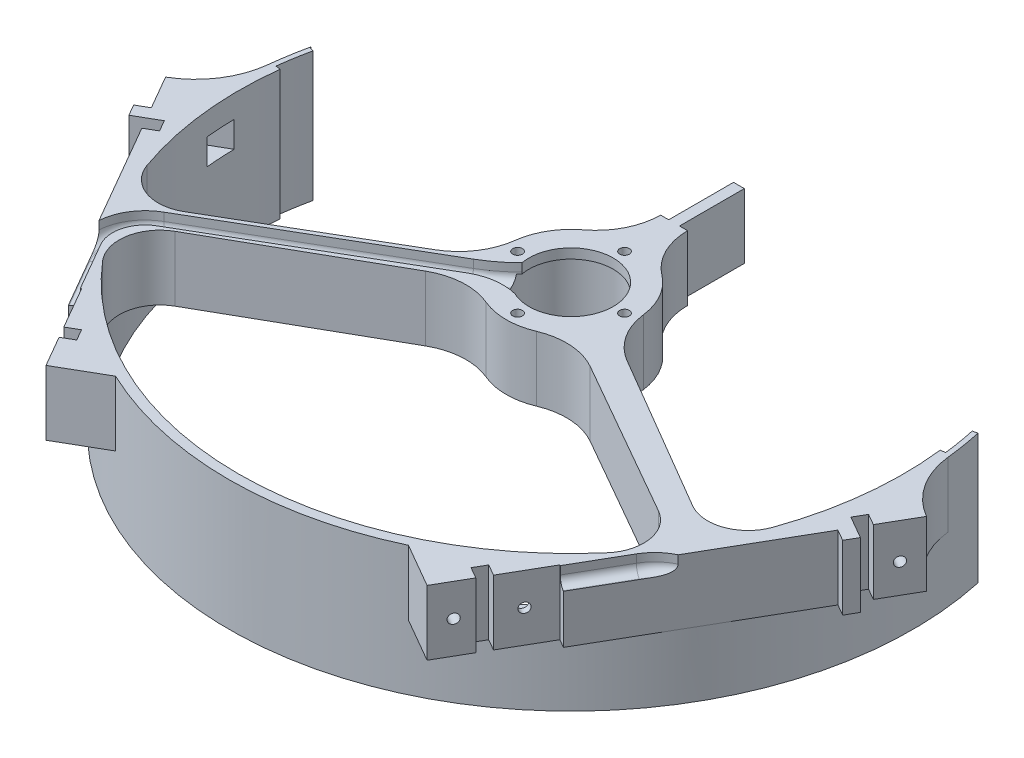
SolidWorks part; units mm, degrees
ref_plane "Plan de face" through (0, 0, 0) normal (0, 0, 1) x (1, 0, 0)
ref_plane "Plan de dessus" through (0, 0, 0) normal (0, 1, 0) x (1, 0, 0)
ref_plane "Plan de droite" through (0, 0, 0) normal (1, 0, 0) x (0, 0, -1)
sketch "Esquisse2" plane through (0, 0, 0) normal (0, 1, 0) x (1, 0, 0)
  circle A0 centre (0, 0) radius 105.5
  dimension "D1" = 211
extrude "Boss.-Extru.1" add sketch "Esquisse2" along normal blind 20
sketch "Esquisse3" plane through (0, 20, 0) normal (0, 1, 0) x (1, 0, 0)
  line L0 (0, 0) -> (0, -37.8201) construction
  line L1 (-22.2901, -5) -> (26.3096, -5) construction
  line L3 (-25.4411, -19.4651) -> (-74.7068, -47.4761)
  line L4 (25.4084, -19.5127) -> (74.6164, -47.6194)
  arc A0 (-78.0463, -66.4457) -> (77.919, -66.5949) centre (0, 0) ccw
  circle A1 centre (0, 0) radius 105.5 construction
  arc A2 (-74.7068, -47.4761) -> (-78.0463, -66.4457) centre (-68.5285, -58.3425) ccw
  arc A3 (77.919, -66.5949) -> (74.6164, -47.6194) centre (68.4167, -58.4736) ccw
  arc A5 (-7.7779, -18.4256) -> (7.7444, -18.4397) centre (0, 0) ccw
  arc A7 (-25.4411, -19.4651) -> (-7.7779, -18.4256) centre (-15.5558, -36.8513) cw
  arc A8 (7.7444, -18.4397) -> (25.4084, -19.5127) centre (15.4889, -36.8795) cw
  point P16 (0, -5)
  dimension "D3" = 102.5
  dimension "D6" = 25
  dimension "D2" = 25
  dimension "D5" = 20
  dimension "D7" = 20
  dimension "D1" = 5
extrude "Enlèv. mat.-Extru.1" cut sketch "Esquisse3" against normal through all
pattern_circular "Répétition circulaire1" count 3 over 360 about axis through (0, 20, 0) along (0, 1, 0) of "Enlèv. mat.-Extru.1"
sketch "Esquisse4" plane through (0, 20, 0) normal (0, 1, 0) x (1, 0, 0)
  circle A0 centre (-16.5, 0) radius 1.5
  circle A1 centre (16.5, 0) radius 1.5
  circle A2 centre (0, 16.5) radius 1.5
  circle A3 centre (0, -16.5) radius 1.5
  dimension "D1" = 3
  dimension "D2" = 3
  dimension "D5" = 3
  dimension "D6" = 3
  dimension "D3" = 16.5
  dimension "D4" = 16.5
  dimension "D7" = 16.5
  dimension "D8" = 16.5
extrude "Enlèv. mat.-Extru.2" cut sketch "Esquisse4" against normal through all
sketch "Esquisse5" plane through (0, 20, 0) normal (0, 1, 0) x (1, 0, 0)
  circle A0 centre (0, 0) radius 13
  dimension "D1" = 26
extrude "Enlèv. mat.-Extru.3" cut sketch "Esquisse5" against normal blind 3
sketch "Esquisse6" plane through (0, 17, 0) normal (0, 1, 0) x (1, 0, 0)
  circle A0 centre (0, 0) radius 14
extrude "Enlèv. mat.-Extru.4" cut sketch "Esquisse6" against normal through all
sketch "Esquisse7" plane through (0, 20, 0) normal (0, 1, 0) x (1, 0, 0)
  line L0 (-16.5, 0) -> (0, -16.5) construction
  line L1 (-73.3003, -42.3791) -> (-18.5313, -10.4184) construction
  line L2 (-78.5478, -40.81) -> (-29.6027, -12.2479) construction
  line L3 (-24.4395, -2.3515) -> (-11.5191, -24.4923) construction
  line L4 (-22.6547, -9.9301) -> (-17.499, -6.9215) construction
  line L5 (-14.9362, -11.215) -> (-21.6686, -15.1437) construction
  line L6 (-78.7767, -48.7003) -> (-18.5358, -13.5465)
  line L7 (-78.7767, -48.7003) -> (-81.4978, -44.0373)
  line L9 (-81.4978, -44.0373) -> (-21.257, -8.8835)
  line L10 (-78.7767, -48.7003) -> (-21.257, -8.8835) construction
  line L11 (-18.5358, -13.5465) -> (-81.4978, -44.0373) construction
  line L12 (-8.25, -8.25) -> (-5.2218, -5.2218) construction
  line L13 (-11.0784, -5.4216) -> (-9.3631, -3.7063) construction
  line L14 (-5.4216, -11.0784) -> (-2.758, -8.4149) construction
  line L15 (-12.4833, -2.3515) -> (-2.758, -12.7041)
  line L16 (-12.4833, -2.3515) -> (-12.7856, -2.3515)
  circle A0 centre (0, 0) radius 13 construction
  arc A1 (-21.257, -8.8835) -> (-12.7856, -2.3515) centre (-42.2756, 27.1348) ccw
  arc A2 (-18.5358, -13.5465) -> (-2.758, -12.7041) centre (-9.8276, -28.4693) cw
  point P14 (-47.6812, -27.4289)
  point P16 (-50.0168, -28.7919)
  dimension "D1" = 4
  dimension "D2" = 2.5
  dimension "D3" = 2.5
  dimension "D4" = 4
  dimension "D5" = 4
extrude "Enlèv. mat.-Extru.5" cut sketch "Esquisse7" against normal blind 5
sketch "Esquisse9" plane through (0, 0, 0) normal (0, -1, 0) x (1, 0, 0)
  line L0 (-117.3657, 7.7167) -> (-111.3657, 18.109)
  line L1 (0, 0) -> (-127.9608, 73.8782) construction
  line L2 (-131.1472, 15.6735) -> (-96.8675, -4.118) construction
  line L4 (-111.3657, 18.109) -> (-107.9016, 16.109)
  line L5 (-107.3657, 25.0372) -> (-103.9016, 23.0372)
  line L6 (-107.9016, 16.109) -> (-103.9016, 23.0372)
  line L7 (-107.3657, 25.0372) -> (-91.3657, 52.75)
  circle A0 centre (0, 0) radius 105.5 construction
  arc A1 (-104.8789, -11.4306) -> (-117.3657, 7.7167) centre (-130.0012, -14.1687) ccw
  arc A2 (-91.3657, 52.75) -> (-104.8789, -11.4306) centre (0, 0) ccw
  point P4 (-91.3657, 52.75)
  point P9 (-117.3657, 7.7167)
  dimension "D3" = 32
  dimension "D2" = 0
  dimension "D4" = 8
  dimension "D5" = 4
  dimension "D6" = 52.75
extrude "Boss.-Extru.4" add sketch "Esquisse9" against normal blind 20
sketch "Esquisse11" plane through (-91.3657, 0, 52.75) normal (-0.866, 0, 0.5) x (0.5, 0, 0.866)
  line L0 (-40, 0) -> (-52, 0) construction
  line L1 (-50, 5) -> (-42, 5)
  line L2 (-50, 5) -> (-50, 13)
  line L3 (-50, 13) -> (-42, 13)
  line L4 (-42, 5) -> (-42, 13)
  line L6 (-52, 20) -> (-52, 0) construction
  dimension "D1" = 8
  dimension "D2" = 8
  dimension "D3" = 5
  dimension "D4" = 2
extrude "Enlèv. mat.-Extru.6" cut sketch "Esquisse11" against normal blind 20
sketch "Esquisse12" plane through (-91.3657, 0, 52.75) normal (-0.866, 0, 0.5) x (0.5, 0, 0.866)
  line L0 (-40, 20) -> (-40, 0) construction
  line L1 (-50.7054, 3.9045) -> (-40, 3.9045)
  line L2 (-50.7054, 3.9045) -> (-50.7054, 16.1116)
  line L3 (-50.7054, 16.1116) -> (-40, 16.1116)
  line L4 (-40, 3.9045) -> (-40, 16.1116)
extrude "Boss.-Extru.5" add sketch "Esquisse12" against normal blind 5
sketch "Esquisse13" plane through (-87.0356, 0, 50.25) normal (0.866, 0, -0.5) x (-0.5, 0, -0.866)
  line L0 (50, 5) -> (42, 5) construction
  line L2 (42, 5) -> (42, 13) construction
  circle A0 centre (46, 9) radius 1.5
  point P7 (42, 10.6595)
  point P8 (44.4531, 9.3264)
  dimension "D1" = 3
  dimension "D2" = 4
  dimension "D3" = 4
extrude "Enlèv. mat.-Extru.7" cut sketch "Esquisse13" against normal through all
sketch "Esquisse22" plane through (0, 20, 0) normal (0, 1, 0) x (1, 0, 0)
  line L0 (-91.3657, -52.75) -> (-78.8757, -74.3833)
  line L1 (-78.8757, -74.3833) -> (-76.2776, -72.8833)
  line L2 (-76.2776, -72.8833) -> (-70.2776, -83.2756)
  line L3 (-58.7776, -103.1942) -> (-45.1731, -95.3396)
  line L4 (-75.8355, -73.3432) -> (-78.0603, -67.6298)
  line L5 (-78.0603, -67.6298) -> (-81.7873, -66.6415)
  line L9 (-68.7776, -85.8737) -> (-58.7776, -103.1942)
  line L10 (-70.2776, -83.2756) -> (-68.7776, -85.8737)
  arc A0 (-91.3657, -52.75) -> (-104.8789, 11.4306) centre (0, 0) ccw construction
  arc A1 (-91.3657, -52.75) -> (-81.7873, -66.6415) centre (0, 0) ccw
  arc A5 (-75.8355, -73.3432) -> (-45.1731, -95.3396) centre (0, 0) ccw
  point P6 (-76.2776, -72.8833)
  dimension "D1" = 3
  dimension "D2" = 35
extrude "Boss.-Extru.11" add sketch "Esquisse22" against normal blind 20
sketch "Esquisse25" plane through (-88.7676, 0, 51.25) normal (-0.866, 0, 0.5) x (0.5, 0, 0.866)
  line L0 (59.98, 0) -> (59.98, 20) construction
  line L1 (49.98, 6) -> (57.98, 6)
  line L2 (49.98, 6) -> (49.98, 14)
  line L3 (49.98, 14) -> (57.98, 14)
  line L4 (57.98, 6) -> (57.98, 14)
  line L5 (24.98, 20) -> (59.98, 20) construction
  dimension "D1" = 2
  dimension "D2" = 8
  dimension "D3" = 8
  dimension "D4" = 6
extrude "Enlèv. mat.-Extru.21" cut sketch "Esquisse25" against normal blind 20
sketch "Esquisse26" plane through (-88.7676, 0, 51.25) normal (-0.866, 0, 0.5) x (0.5, 0, 0.866)
  line L1 (49.98, 6) -> (57.98, 6)
  line L2 (49.98, 6) -> (49.98, 14)
  line L3 (49.98, 14) -> (57.98, 14)
  line L4 (57.98, 6) -> (57.98, 14)
extrude "Boss.-Extru.12" add sketch "Esquisse26" against normal blind 4
sketch "Esquisse28" plane through (-85.3035, 0, 49.25) normal (0.866, 0, -0.5) x (-0.5, 0, -0.866)
  line L0 (-49.98, 14) -> (-49.98, 6) construction
  line L1 (-49.98, 6) -> (-57.98, 6) construction
  circle A0 centre (-53.98, 10) radius 1.5
  dimension "D1" = 3
  dimension "D2" = 4
  dimension "D3" = 4
extrude "Enlèv. mat.-Extru.22" cut sketch "Esquisse28" against normal through all
sketch "Esquisse29" plane through (-88.7676, 0, 51.25) normal (-0.866, 0, 0.5) x (0.5, 0, 0.866)
  line L0 (24.98, 0) -> (59.98, 0) construction
  line L1 (44.98, 0) -> (48.98, 0)
  line L2 (44.98, 0) -> (44.98, 20)
  line L3 (44.98, 20) -> (48.98, 20)
  line L4 (48.98, 0) -> (48.98, 20)
  line L5 (24.98, 20) -> (59.98, 20) construction
  line L7 (59.98, 0) -> (59.98, 20) construction
  dimension "D1" = 4
  dimension "D2" = 11
extrude "Enlèv. mat.-Extru.23" cut sketch "Esquisse29" against normal blind 4
sketch "Esquisse30" plane through (-88.7676, 0, 51.25) normal (-0.866, 0, 0.5) x (0.5, 0, 0.866)
  line L0 (44.98, 20) -> (44.98, 0) construction
  line L1 (41.98, 6) -> (33.98, 6)
  line L2 (41.98, 6) -> (41.98, 14)
  line L3 (41.98, 14) -> (33.98, 14)
  line L4 (33.98, 6) -> (33.98, 14)
  line L5 (24.98, 20) -> (44.98, 20) construction
  dimension "D1" = 3
  dimension "D2" = 8
  dimension "D3" = 8
  dimension "D4" = 6
extrude "Enlèv. mat.-Extru.24" cut sketch "Esquisse30" against normal blind 23
sketch "Esquisse31" plane through (-88.7676, 0, 51.25) normal (-0.866, 0, 0.5) x (0.5, 0, 0.866)
  line L1 (33.98, 6) -> (41.98, 6)
  line L2 (33.98, 6) -> (33.98, 14)
  line L3 (33.98, 14) -> (41.98, 14)
  line L4 (41.98, 6) -> (41.98, 14)
extrude "Boss.-Extru.13" add sketch "Esquisse31" against normal blind 2
sketch "Esquisse32" plane through (-87.0356, 0, 50.25) normal (0.866, 0, -0.5) x (-0.5, 0, -0.866)
  line L0 (-33.98, 6) -> (-41.98, 6) construction
  line L1 (-33.98, 14) -> (-33.98, 6) construction
  circle A0 centre (-37.98, 10) radius 1.5
  dimension "D1" = 3
  dimension "D2" = 4
  dimension "D3" = 4
extrude "Enlèv. mat.-Extru.25" cut sketch "Esquisse32" against normal blind 22
sketch "Esquisse33" plane through (12.49, 0, 21.6333) normal (0.5, 0, 0.866) x (0.866, 0, -0.5)
  line L1 (-105.5, 20) -> (-102.5, 20)
  line L2 (-105.5, 20) -> (-105.5, 0)
  line L3 (-105.5, 0) -> (-102.5, 0)
  line L4 (-102.5, 20) -> (-102.5, 0)
extrude "Boss.-Extru.14" add sketch "Esquisse33" along normal blind 5
mirror "Symétrie1" about plane through (0, 0, 0) normal (1, 0, 0) of "Enlèv. mat.-Extru.25", "Boss.-Extru.13", "Enlèv. mat.-Extru.24", "Enlèv. mat.-Extru.22", "Boss.-Extru.12", "Enlèv. mat.-Extru.21", "Boss.-Extru.5", "Enlèv. mat.-Extru.6", "Boss.-Extru.4", "Enlèv. mat.-Extru.7", "Boss.-Extru.11", "Enlèv. mat.-Extru.23", "Boss.-Extru.14"
sketch "Esquisse20" plane through (-87.9016, 0, 50.75) normal (-0.866, 0, 0.5) x (0.5, 0, 0.866)
  line L0 (-32, 20) -> (-40, 20) construction
  line L1 (-40, 0) -> (-36, 0)
  line L2 (-40, 0) -> (-40, 20)
  line L3 (-40, 20) -> (-36, 20)
  line L4 (-36, 0) -> (-36, 20)
extrude "Boss.-Extru.9" add sketch "Esquisse20" along normal blind 8
sketch "Esquisse21" plane through (87.9016, 0, 50.75) normal (0.866, 0, 0.5) x (0.5, 0, -0.866)
  line L0 (32, 0) -> (40, 0) construction
  line L1 (32, 20) -> (36, 20)
  line L2 (32, 20) -> (32, 0)
  line L3 (32, 0) -> (36, 0)
  line L4 (36, 20) -> (36, 0)
extrude "Boss.-Extru.10" add sketch "Esquisse21" along normal blind 8
sketch "Esquisse36" plane through (0, 0, 0) normal (0, -1, 0) x (1, 0, 0)
  circle A0 centre (0, 0) radius 105.5
  circle A1 centre (0, 0) radius 102.5
extrude "Boss.-Extru.16" add sketch "Esquisse36" along normal blind 20 contours A1 | A0
sketch "Esquisse37" plane through (0, 20, 0) normal (0, 1, 0) x (1, 0, 0)
  line L0 (-78.9735, -48.8139) -> (-78.7767, -48.7003)
  line L1 (-76.3757, -78.7134) -> (-107.3657, -25.0372) construction
  line L3 (-82.6337, -62.4742) -> (-74.0374, -77.3634)
  line L4 (-74.0374, -77.3634) -> (-76.3757, -78.7134)
  line L5 (-76.3757, -78.7134) -> (-89.3273, -56.2805)
  line L9 (-78.7767, -48.7003) -> (-81.4978, -44.0373)
  line L10 (-73.7776, -77.2134) -> (-76.3757, -78.7134) construction
  arc A0 (-82.6337, -62.4742) -> (-78.9735, -48.8139) centre (-73.9735, -57.4742) cw
  arc A1 (-81.4978, -44.0373) -> (-89.3273, -56.2805) centre (-73.9735, -57.4742) ccw
  dimension "D2" = 10
  dimension "D1" = 2.7
  dimension "D3" = 0
extrude "Enlèv. mat.-Extru.26" cut sketch "Esquisse37" against normal blind 5
sketch "Esquisse38" plane through (0, 20, 0) normal (0, 1, 0) x (-1, 0, 0)
  line L0 (-78.8757, 74.3833) -> (-76.3757, 78.7134)
  line L2 (-82.6324, 62.4765) -> (-76.5374, 73.0333)
  line L4 (-78.8757, 74.3833) -> (-89.3259, 56.2831)
  line L5 (-73.7776, 77.2134) -> (-76.3757, 78.7134) construction
  line L6 (-76.5374, 73.0333) -> (-74.0374, 77.3634)
  line L7 (-74.0374, 77.3634) -> (-76.3757, 78.7134)
  arc A0 (-89.3259, 56.2831) -> (-82.6324, 62.4765) centre (-95.9692, 70.1765) ccw
  point P8 (-95.9692, 70.1765)
  dimension "D1" = 2.7
  dimension "D4" = 15.4
extrude "Enlèv. mat.-Extru.27" cut sketch "Esquisse38" against normal blind 5
fillet "Congé2" radius 2.5 5 edges at (-13.6071, 15, 11.6099) (-48.6563, 15, 31.1234) (-78.8751, 15, 48.7571) (-83.6327, 15, 54.886) (-78.3356, 15, 69.9188)
fillet "Congé4" radius 2.5 3 edges at (-51.3774, 15, 26.4604) (-17.2825, 15, 6.2485) (-86.9476, 15, 49.1773)
fillet "Congé5" radius 2.5 2 edges at (78.3349, 15, 69.9199) (85.5102, 15, 58.873)
sketch "Esquisse39" plane through (0, 20, 0) normal (0, 1, 0) x (1, 0, 0)
  line L0 (-101.7887, 12.0544) -> (-4.1367, 31.7652)
  line L1 (1.6943, 31.762) -> (1.6943, 51.762)
  line L2 (1.6943, 51.762) -> (-1.6367, 51.762)
  line L3 (-1.6367, 51.762) -> (-1.6367, 31.7638)
  line L4 (4.1943, 31.7607) -> (1.6943, 31.762)
  line L5 (1.6943, 31.762) -> (1.6847, 31.674)
  line L6 (-4.1367, 31.7652) -> (-1.6367, 31.7638)
  line L7 (101.6442, 12.0838) -> (4.1943, 31.7607)
  line L8 (101.6442, 12.0838) -> (103.2728, 12.2774)
  line L9 (-101.6262, 22.0934) -> (-102.978, 22.3872)
  line L10 (-101.7887, 12.0544) -> (-103.2783, 12.2308)
  line L11 (-102.978, 22.3872) -> (-123.4781, 238.8457)
  line L12 (101.6162, 22.1392) -> (103.0818, 22.4586)
  line L13 (-123.4781, 238.8457) -> (174.2735, 41.762)
  line L14 (174.2735, 41.762) -> (103.0818, 22.4586)
  arc A0 (104.8789, 11.4306) -> (-104.8789, 11.4306) centre (0, 0) ccw construction
  arc A1 (103.2728, 12.2774) -> (101.6162, 22.1392) centre (0, 0) ccw
  arc A2 (-18.5205, 100.8129) -> (-96.6324, -34.1824) centre (0, 0) ccw construction
  arc A3 (-101.6262, 22.0934) -> (-103.2783, 12.2308) centre (0, 0) ccw
  point P4 (101.6162, 22.1392)
  point P8 (101.6442, 12.0838)
  point P10 (-101.7887, 12.0544)
  point P17 (-101.6262, 22.0934)
  point P19 (103.2728, 12.2774)
  point P20 (103.0818, 22.4586)
  point P31 (-103.2783, 12.2308)
  dimension "D4" = 1.5
  dimension "D1" = 2.5
  dimension "D2" = 2.5
  dimension "D3" = 20
  dimension "D5" = 10
  dimension "D6" = 10
extrude "Enlèv. mat.-Extru.28" cut sketch "Esquisse39" against normal through all contours L9 A3 L10 L0 L6 L3 L2 L1 L4 L7 L8 A1 L12 L14 L13 L11 region at (-12.7389, 20, -96.4605)
